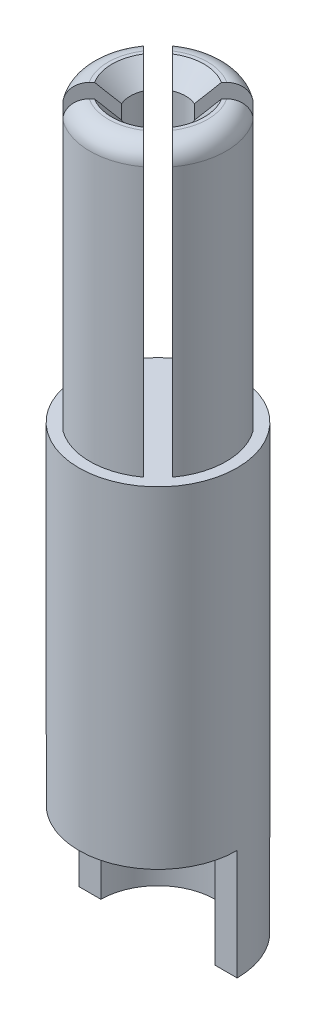
SolidWorks part; units mm, degrees
material "Copper"
ref_plane "Plano frontal" through (0, 0, 0) normal (0, 0, 1) x (1, 0, 0)
ref_plane "Plano superior" through (0, 0, 0) normal (0, 1, 0) x (1, 0, 0)
ref_plane "Plano direito" through (0, 0, 0) normal (1, 0, 0) x (0, 0, -1)
sketch "Esboço1" plane through (0, 0, 0) normal (0, 0, 1) x (1, 0, 0)
  line L0 (0, 10) -> (0, 19.8)
  line L1 (0, 0) -> (2.15, 0) construction
  line L2 (2.15, 0) -> (2.15, 19.8)
  line L3 (2.15, 19.8) -> (0, 19.8)
  line L4 (1.55, 0) -> (1.55, 7.5)
  line L5 (1.55, 0) -> (2.15, 0)
  line L6 (1.55, 7.5) -> (0, 10)
  dimension "D1" = 19.8
  dimension "D2" = 2.15
  dimension "D3" = 0.6
  dimension "D4" = 10
  dimension "D5" = 2.5
revolve "Revolução1" add sketch "Esboço1" angle 360 about L0
sketch "Esboço2" plane through (0, 19.8, 0) normal (0, 1, 0) x (1, 0, 0)
  line L0 (-1.0992, 1.4881) -> (1.0992, 1.4881) construction
  line L1 (-1.0992, 1.4881) -> (-0.2989, 0.6878)
  line L2 (1.0992, 1.4881) -> (0.2989, 0.6878)
  line L3 (-1.4881, 1.0992) -> (-1.4881, -1.0992) construction
  line L4 (1.4881, 1.0992) -> (1.4881, -1.0992) construction
  line L5 (1.0992, -1.4881) -> (-1.0992, -1.4881) construction
  line L6 (-1.4881, 1.0992) -> (-0.6878, 0.2989)
  line L7 (-1.4881, -1.0992) -> (-0.6878, -0.2989)
  line L8 (1.0992, -1.4881) -> (0.2989, -0.6878)
  line L9 (1.4881, 1.0992) -> (0.6878, 0.2989)
  line L10 (1.4881, -1.0992) -> (0.6878, -0.2989)
  line L11 (-1.0992, -1.4881) -> (-0.2989, -0.6878)
  arc A0 (-1.4881, 1.0992) -> (-1.4881, -1.0992) centre (0, 0) ccw
  arc A1 (-0.6878, 0.2989) -> (-0.6878, -0.2989) centre (0, 0) ccw
  circle A2 centre (0, 0) radius 2.15
  circle A3 centre (0, 0) radius 1.85 construction
  arc A4 (1.0992, 1.4881) -> (-1.0992, 1.4881) centre (0, 0) ccw
  arc A5 (1.4881, -1.0992) -> (1.4881, 1.0992) centre (0, 0) ccw
  arc A6 (-1.0992, -1.4881) -> (1.0992, -1.4881) centre (0, 0) ccw
  circle A7 centre (0, 0) radius 0.75 construction
  arc A8 (0.2989, 0.6878) -> (-0.2989, 0.6878) centre (0, 0) ccw
  arc A9 (0.6878, -0.2989) -> (0.6878, 0.2989) centre (0, 0) ccw
  arc A10 (-0.2989, -0.6878) -> (0.2989, -0.6878) centre (0, 0) ccw
  dimension "D1" = 3.7
  dimension "D3" = 0.55
  dimension "D2" = 1.1
extrude "Corte-extrusão3" cut sketch "Esboço2" against normal blind 7.8
sketch "Esboço3" plane through (0, 0, 0) normal (0, -1, 0) x (1, 0, 0)
  line L1 (-2.3943, 2.452) -> (2.3943, 2.452)
  line L2 (-2.3943, 2.452) -> (-2.3943, 0)
  line L3 (-2.3943, 0) -> (2.3943, 0)
  line L4 (2.3943, 2.452) -> (2.3943, 0)
extrude "Corte-extrusão4" cut sketch "Esboço3" against normal blind 3
other "PontoC1" parameters "Diâmetro"=5, "ComprimentoAdaptador"=0
ref_axis "Eixo1" through (0, -7, 0) along (0, 1, 0)
chamfer "Chanfro1" distance 0.5 angle 45 4 edges at (0, 19.8, 0.75) (0.75, 19.8, 0) (0, 19.8, -0.75) (-0.75, 19.8, 0)
fillet "Filete1" radius 0.5 4 edges at (1.85, 19.8, 0) (0, 19.8, -1.85) (0, 19.8, 1.85) (-1.85, 19.8, 0)
